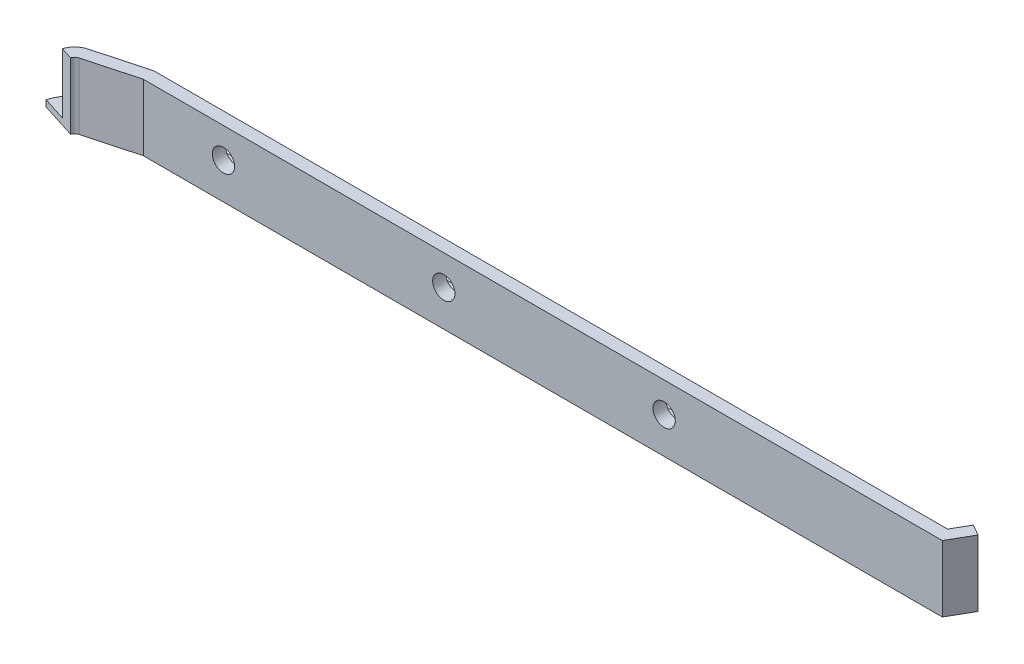
SolidWorks part; units mm, degrees
material "PET"
ref_plane "Front Plane" through (0, 0, 0) normal (0, 0, 1) x (1, 0, 0)
ref_plane "Top Plane" through (0, 0, 0) normal (0, 1, 0) x (1, 0, 0)
ref_plane "Right Plane" through (0, 0, 0) normal (1, 0, 0) x (0, 0, -1)
sketch "Sketch1" plane through (0, 0, 0) normal (0, 0, 1) x (1, 0, 0)
  circle A0 centre (18.725, 0) radius 1.4732 construction
  circle A1 centre (-16.275, 0) radius 1.4732 construction
  circle A2 centre (-51.275, 0) radius 1.4732 construction
  circle A3 centre (18.725, 0) radius 1.4732 construction
  circle A4 centre (-16.275, 0) radius 1.4732 construction
  circle A5 centre (-51.275, 0) radius 1.4732 construction
sketch "Sketch2" plane through (0, -4.7625, 0) normal (0, -1, 0) x (1, 0, 0)
  line L0 (-64.275, 0) -> (-72.5616, 2.2352) construction
  line L1 (61.75, 0) -> (-64.275, 0) construction
  line L2 (77.4756, -27.2375) -> (61.75, 0) construction
  line L3 (77.4756, -27.2375) -> (61.75, 0) construction
  line L4 (61.75, 0) -> (-64.275, 0)
  line L5 (-64.275, 0) -> (-72.5616, 2.2352)
  line L6 (61.75, 0) -> (63.25, -2.5981)
  arc A0 (-74.6395, 4.2232) -> (-72.5616, 2.2352) centre (-71.7803, 5.1317) ccw construction
  arc A1 (-74.6395, 4.2232) -> (-72.5616, 2.2352) centre (-71.7803, 5.1317) ccw
  dimension "D1" = 3
extrude "Extrude-Thin1" add sketch "Sketch2" against normal up to surface (9.525 mm away) thin thin type one direction reverse wall 2
sketch "Sketch3" plane through (0, 0, 0) normal (0, 0, -1) x (-1, 0, 0)
  circle A0 centre (51.275, 0) radius 1.65
  circle A1 centre (16.275, 0) radius 1.65
  circle A2 centre (-18.725, 0) radius 1.65
  dimension "D1" = 3.3
extrude "Cut-Extrude1" cut sketch "Sketch3" against normal through all draft 3.5 draft outward yes
extrude "Extrude-Thin2" add sketch "Sketch2<2>" along normal blind 1 thin thin type two direction wall 4 second wall 2
sketch "Sketch2<2>" plane through (0, -4.7625, 0) normal (0, -1, 0) x (1, 0, 0) same geometry as "Sketch2"
equation "\"D6@Extrude-Thin2\"=\"D5@Extrude-Thin1\""
